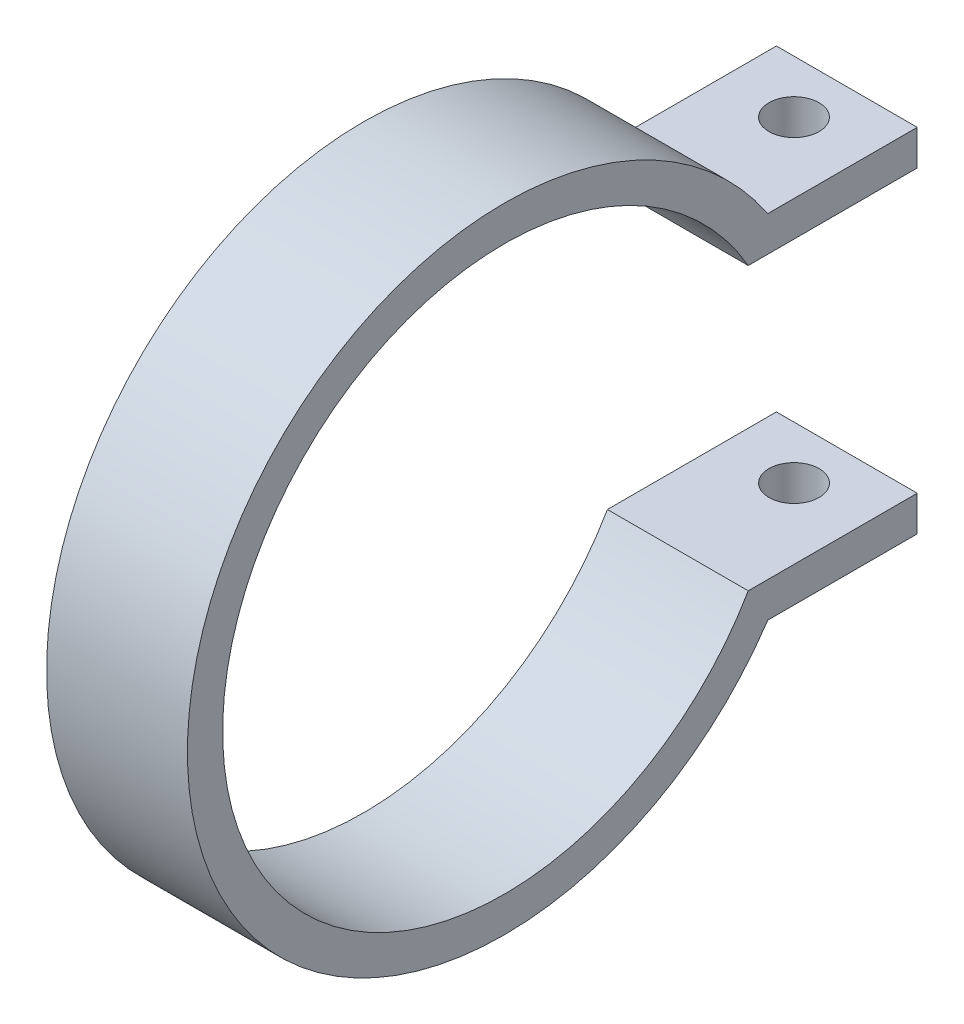
SolidWorks part; units mm, degrees
material "6061-T6 (SS)"
ref_plane "Front Plane" through (0, 0, 0) normal (1, 0, 0) x (0, 1, 0)
ref_plane "Top Plane" through (0, 0, 0) normal (0, 0, 1) x (0, 1, 0)
ref_plane "Right Plane" through (0, 0, 0) normal (0, 1, 0) x (-1, 0, 0)
sketch "Sketch2" plane through (0, 0, 0) normal (1, 0, 0) x (0, 1, 0)
  line L0 (-6.35, -10.9985) -> (6.35, -10.9985) construction
  line L1 (-6.35, -10.9985) -> (-6.35, -18.6185)
  line L2 (6.35, -10.9985) -> (6.35, -18.6185)
  line L3 (-7.9375, -11.8798) -> (-7.9375, -18.6185)
  line L4 (-7.9375, -18.6185) -> (-6.35, -18.6185)
  line L5 (6.35, -18.6185) -> (7.9375, -18.6185)
  line L6 (7.9375, -18.6185) -> (7.9375, -11.8798)
  arc A0 (6.35, -10.9985) -> (-6.35, -10.9985) centre (0, 0) ccw
  arc A1 (7.9375, -11.8798) -> (-7.9375, -11.8798) centre (0, 0) ccw
  dimension "D2" = 12.7
  dimension "D4" = 14.2875
  dimension "D1" = 12.7
  dimension "D3" = 7.62
  dimension "D5" = 1.5875
  dimension "D6" = 1.5875
extrude "Boss-Extrude1" add sketch "Sketch2" along normal blind 6.35
sketch "Sketch3" plane through (0, -7.9375, 0) normal (0, -1, 0) x (1, 0, 0)
  line L1 (3.175, -11.8798) -> (3.175, -18.6185) construction
  line L2 (6.35, -11.8798) -> (0, -11.8798) construction
  line L3 (6.35, -18.6185) -> (0, -18.6185) construction
  point P9 (3.175, -16.2373)
  point P18 (0, 0)
  point P19 (3.175, -16.2653)
  dimension "D1" = 2.3813
hole_wizard "Tap Drill for #4-40 Tap1" positions "Sketch3" profile "Sketch4" hole size "#4-40" standard "ANSI Inch" end condition through all
sketch "Sketch4" plane through (3.175, -7.9375, -16.2373) normal (1, 0, 0) x (0, 0, -1)
  line L0 (0, 0) -> (0, 22.225)
  line L1 (0, 22.225) -> (1.1303, 22.225)
  line L2 (1.1303, 22.225) -> (1.1303, 0)
  line L5 (1.1303, 0) -> (0, 0)
  line L11 (0, -6.35) -> (0, 107.95) construction
  dimension "Thru Hole Dia." = 2.2606
  dimension "Thru Hole Depth" = 22.225
